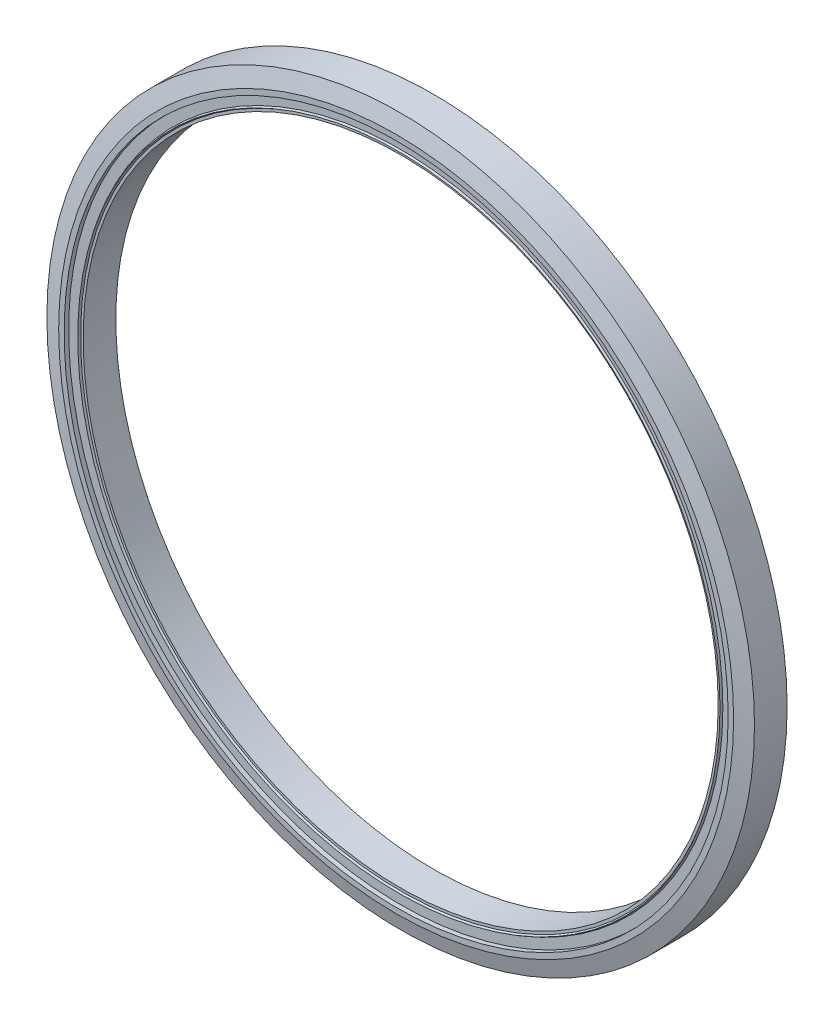
SolidWorks part; units mm, degrees
material "HPU"
ref_plane "Front Plane" through (0, 0, 0) normal (0, 0, 1) x (1, 0, 0)
ref_plane "Top Plane" through (0, 0, 0) normal (0, 1, 0) x (1, 0, 0)
ref_plane "Right Plane" through (0, 0, 0) normal (1, 0, 0) x (0, 0, -1)
sketch "Sketch2" plane through (0, 0, 0) normal (1, 0, 0) x (0, 0, -1)
  line L0 (0, 0) -> (0, 7.502) construction
  line L1 (-0.9, 19.5) -> (0.9, 19.5)
  line L2 (-1.15, 18.6) -> (-0.9, 19.5)
  line L3 (-0.9, 17.5) -> (0.9, 17.5)
  line L4 (-1, 17.7) -> (1, 17.7) construction
  line L5 (0, 0) -> (5.5331, 0) construction
  line L6 (1, 17.7) -> (0.9, 17.6423)
  line L7 (1.15, 18.6) -> (0.9, 19.5)
  line L8 (1.15, 18.3) -> (0.9, 18.3)
  line L9 (0.9, 18.3) -> (0.9, 17.7577)
  line L10 (1, 17.7) -> (0.9, 17.7577)
  line L11 (1.15, 18.3) -> (1.15, 18.6)
  line L12 (-1, 17.7) -> (-0.9, 17.7577)
  line L13 (-0.9, 18.3) -> (-0.9, 17.7577)
  line L14 (-1.15, 18.3) -> (-0.9, 18.3)
  line L15 (-1.15, 18.3) -> (-1.15, 18.6)
  line L16 (-1, 17.7) -> (-0.9, 17.6423)
  line L17 (-0.9, 17.6423) -> (-0.9, 17.5)
  line L18 (0.9, 17.6423) -> (0.9, 17.5)
  dimension "D1" = 2.3
  dimension "D2" = 39
  dimension "D3" = 35
  dimension "D4" = 37.2
  dimension "D5" = 1.8
  dimension "D6" = 1.8
  dimension "D7" = 0.3
  dimension "D8" = 35.4
  dimension "D9" = 2
  dimension "D10" = 60
  dimension "D11" = 0.2
  dimension "D12" = 2
  dimension "D13" = 1.1
revolve "Revolve2" add sketch "Sketch2" angle 360 about L5
ref_axis "Axis1" through (0, 0, -1.265) along (0, 0, 1)
